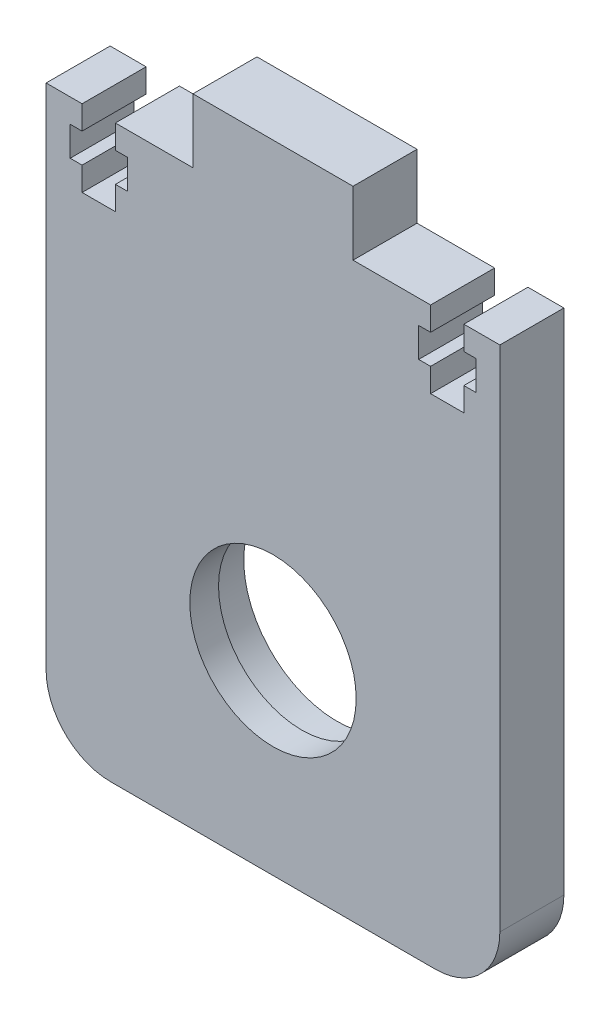
SolidWorks part; units mm, degrees
ref_plane "Front Plane" through (0, 0, 0) normal (0, 0, 1) x (1, 0, 0)
ref_plane "Top Plane" through (0, 0, 0) normal (0, 1, 0) x (1, 0, 0)
ref_plane "Right Plane" through (0, 0, 0) normal (1, 0, 0) x (0, 0, -1)
sketch "Sketch12" plane through (0, 0, 0) normal (0, 0, 1) x (1, 0, 0)
  line L0 (62.1258, 0) -> (62.1258, 113.63)
  line L1 (62.1258, 113.63) -> (152.1258, 113.63)
  line L2 (62.1258, 0) -> (152.1258, 0)
  line L3 (152.1258, 113.63) -> (152.1258, 0)
  dimension "D1" = 113.63
  dimension "D2" = 90
extrude "Boss-Extrude10" add sketch "Sketch12" along normal blind 12.7 separate body contours L1 L3 L2 L0
sketch "Sketch15" plane through (0, 0, 12.7) normal (0, 0, 1) x (1, 0, 0)
  line L0 (62.1258, 0) -> (152.1258, 0) construction
  circle A0 centre (107.1258, 38.6276) radius 25.4
  point P7 (107.1258, 0)
  dimension "D1" = 50.8
  dimension "D2" = 38.6276
sketch "Sketch24" plane through (0, 0, 12.7) normal (0, 0, 1) x (1, 0, 0)
  line L0 (62.1258, 113.63) -> (62.1258, 109.63)
  line L1 (62.1258, 0) -> (62.1258, 113.63) construction
  line L2 (62.1258, 109.63) -> (152.1258, 109.63)
  line L3 (152.1258, 113.63) -> (152.1258, 0) construction
  line L4 (152.1258, 109.63) -> (152.1258, 113.63)
  line L5 (152.1258, 113.63) -> (62.1258, 113.63)
  dimension "D1" = 4
sketch "Sketch25" plane through (0, 0, 12.7) normal (0, 0, 1) x (1, 0, 0)
  circle A0 centre (107.1258, 38.6276) radius 18.5
  dimension "D1" = 37
extrude "Cut-Extrude1" cut sketch "Sketch25" against normal through all
sketch "Sketch26" plane through (0, 0, 12.7) normal (0, 0, 1) x (1, 0, 0)
  circle A0 centre (107.1258, 38.6276) radius 16.5
  circle A1 centre (107.1258, 38.6276) radius 18.5
  dimension "D1" = 37
  dimension "D2" = 2
extrude "Boss-Extrude15" add sketch "Sketch26" against normal blind 5.7
fillet "Fillet1" radius 12.8 2 edges at (152.1258, 0, 6.35) (62.1258, 0, 6.35)
sketch "Sketch27" plane through (0, 0, 0) normal (0, 0, -1) x (-1, 0, 0)
  line L0 (-69.2638, 113.63) -> (-69.2638, 108.931)
  line L1 (-152.1258, 113.63) -> (-62.1258, 113.63) construction
  line L2 (-69.2638, 108.931) -> (-66.9018, 108.931)
  line L3 (-66.9018, 108.931) -> (-66.9018, 103.089)
  line L4 (-66.9018, 103.089) -> (-69.2638, 103.089)
  line L5 (-69.2638, 103.089) -> (-69.2638, 98.39)
  line L6 (-69.2638, 98.39) -> (-75.8678, 98.39)
  line L7 (-75.8678, 98.39) -> (-75.8678, 103.089)
  line L8 (-75.8678, 103.089) -> (-78.2298, 103.089)
  line L9 (-78.2298, 103.089) -> (-78.2298, 108.931)
  line L10 (-78.2298, 108.931) -> (-75.8678, 108.931)
  line L11 (-75.8678, 108.931) -> (-75.8678, 113.63)
  line L12 (-75.8678, 113.63) -> (-69.2638, 113.63)
  line L13 (-138.3838, 108.931) -> (-138.3838, 113.63)
  line L15 (-107.1258, 113.63) -> (-107.1258, 67.3255)
  line L28 (-136.0218, 108.931) -> (-138.3838, 108.931)
  line L29 (-136.0218, 103.089) -> (-136.0218, 108.931)
  line L30 (-138.3838, 103.089) -> (-136.0218, 103.089)
  line L31 (-138.3838, 98.39) -> (-138.3838, 103.089)
  line L32 (-144.9878, 98.39) -> (-138.3838, 98.39)
  line L33 (-144.9878, 103.089) -> (-144.9878, 98.39)
  line L34 (-147.3498, 103.089) -> (-144.9878, 103.089)
  line L35 (-147.3498, 108.931) -> (-147.3498, 103.089)
  line L36 (-144.9878, 108.931) -> (-147.3498, 108.931)
  line L37 (-144.9878, 113.63) -> (-144.9878, 108.931)
  line L38 (-138.3838, 113.63) -> (-144.9878, 113.63)
  line L39 (-72.5658, 113.63) -> (-107.1258, 113.63)
  line L40 (-107.1258, 113.63) -> (-141.6858, 113.63)
  point P22 (-72.5658, 113.63)
  point P29 (-141.6858, 113.63)
  line M19 (-62.1258, 113.63) -> (-152.1258, 113.63)
  dimension "D1" = 6.604
  dimension "D2" = 11.328
  dimension "D3" = 5.842
  dimension "D4" = 15.24
  dimension "D5" = 69.12
ref_axis "Axis2" through (107.1258, 113.63, 0) along (0, -1, 0)
extrude "Cut-Extrude2" cut sketch "Sketch27" against normal through all contours L11 L10 L9 L8 L7 L6 L5 L4 L3 L2 L0 M19 | L37 L36 L35 L34 L33 L32 L31 L30 L29 L28 L13 M19 region at (141.6858, 106.01, 0) region at (72.5658, 106.01, 0)
sketch "Sketch28" plane through (0, 113.63, 0) normal (0, 1, 0) x (1, 0, 0)
  line L0 (107.1258, 0) -> (91.2508, 0)
  line L1 (75.8678, 0) -> (138.3838, 0) construction
  line L2 (91.2508, 0) -> (91.2508, -12.7)
  line L3 (81.7258, -12.7) -> (132.5258, -12.7) construction
  line L4 (91.2508, -12.7) -> (123.0008, -12.7)
  line L5 (123.0008, -12.7) -> (123.0008, 0)
  line L6 (123.0008, 0) -> (107.1258, 0)
  dimension "D1" = 31.75
extrude "Boss-Extrude16" add sketch "Sketch28" along normal blind 12.7
